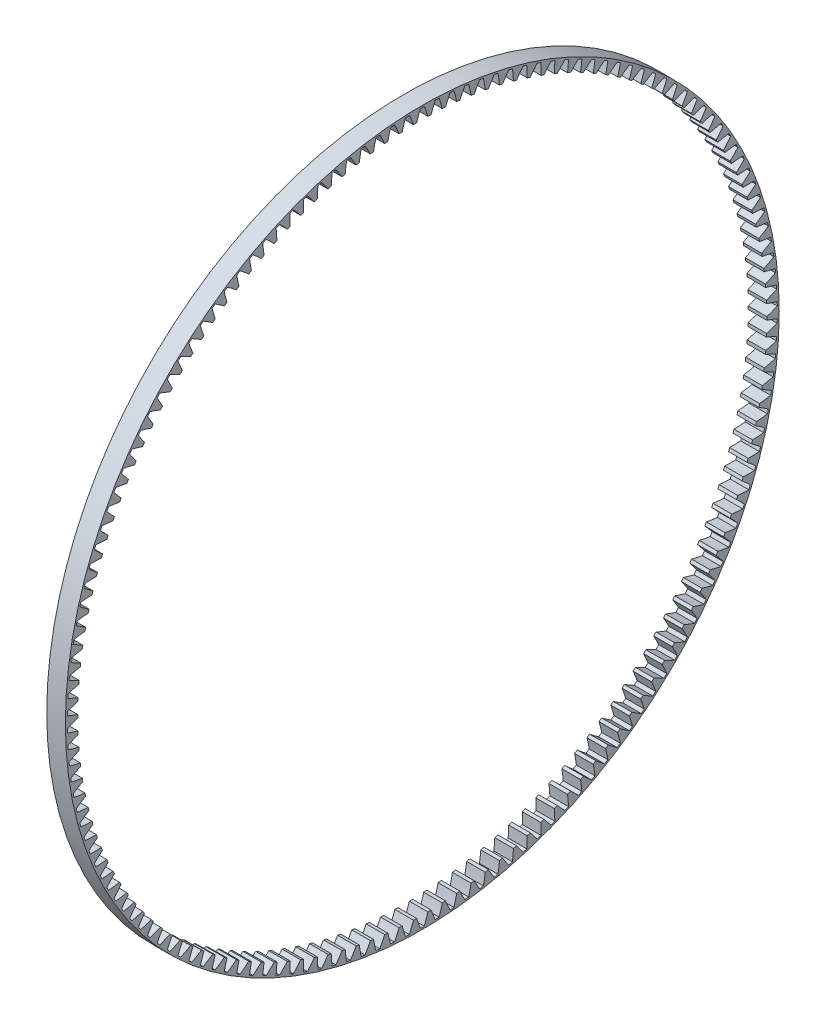
SolidWorks part; units mm, degrees
ref_plane "Plane1" through (0, 0, 0) normal (0, 0, 1) x (1, 0, 0)
ref_plane "Plane2" through (0, 0, 0) normal (0, 1, 0) x (1, 0, 0)
ref_plane "Plane3" through (0, 0, 0) normal (1, 0, 0) x (0, 0, -1)
sketch "HoldingSke" plane through (0, 0, 0) normal (0, 1, 0) x (1, 0, 0)
  line L0 (0, 0) -> (-0.2887, -0.1667)
  line L1 (-15, 0) -> (100, 0) construction
  line L2 (0, 0) -> (-2.1039, 2.3779)
  line L3 (0, 0) -> (-11.863, 4.5341)
  line L4 (0, 0) -> (-7.479, 4.318)
  line L5 (0, 0) -> (-23.7986, -8.8762)
  line L6 (0, 0) -> (-10.5278, -7.1032)
  line L7 (-2.1039, 2.3779) -> (3.3635, 27.1825)
  line L8 (-76.2, 5.3779) -> (-54.61, 5.3779)
  line L9 (-71.009, 38.7566) -> (-53.1078, 45.2721)
  line L10 (-76.2, 71.12) -> (104.1128, 71.12)
  line L11 (0, 0) -> (-12, 0)
  line L12 (-76.2, 101.6) -> (-76.093, 101.6)
  line L13 (24.9733, 27.94) -> (52.9518, 28.4284)
  line L14 (24.9733, 27.94) -> (24.9743, 27.94)
  line L15 (24.9733, 27.94) -> (100.4006, 29.5858)
  circle A0 centre (0, 0) radius 230
  circle A1 centre (0, 0) radius 12.7
  circle A2 centre (0, 0) radius 12.7
  dimension "Num_teeth" = 150
  dimension "Pitch_radius" = 180.3128
  dimension "Width" = 12
  dimension "Diameter" = 460
sketch "BasProSke" plane through (0, 0, 0) normal (0, 1, 0) x (1, 0, 0)
  line L0 (-10, 0) -> (60, 0) construction
  line L1 (0, 222) -> (0, 230)
  line L2 (0, 222) -> (12, 222)
  line L3 (12, 222) -> (12, 230)
  line L4 (12, 230) -> (0, 230)
  dimension "Thickness" = 12
  dimension "Diameter" = 460
revolve "Base-Revolve" add sketch "BasProSke" angle 360 about L0
sketch "TooCutSke" plane through (0, 0, 0) normal (1, 0, 0) x (0, 0, -1)
  line L3 (2.6237, 224.9847) -> (2.6237, 53.6633) construction
  line L4 (0, 0) -> (0, 59.563) construction
  line L5 (0, 0) -> (-1.4309, 68.3125) construction
  line L6 (-103.6779, 188.1578) -> (33.8494, 191.0385) construction
  circle A0 centre (0, 0) radius 225 construction
  circle A1 centre (0, 0) radius 228.751 construction
  circle A2 centre (0, 0) radius 190.2878 construction
  circle A3 centre (0, 0) radius 221.9746 construction
  arc A4 (3.6285, 221.9449) -> (1.2445, 228.7476) centre (-103.6779, 188.1578) ccw
  arc A5 (3.6285, 221.9449) -> (-3.6285, 221.9449) centre (0, 0) ccw
  arc A6 (1.2445, 228.7476) -> (-1.2445, 228.7476) centre (0, 0) ccw
  arc A7 (-1.2445, 228.7476) -> (-3.6285, 221.9449) centre (103.6779, 188.1578) ccw
extrude "ToothCut" cut sketch "TooCutSke" along normal through all
fillet "Breaks" [suppressed] radius 0.3
fillet "RootFillets" [suppressed] radius 0.751
pattern_circular "TeethCuts" count 150 every 2.4 about axis through (-10, 0, 0) along (1, 0, 0) of "RootFillets", "Breaks", "ToothCut"
equation "' \"Module@HoldingSke\" = 6.35"
equation "' \"Num_teeth@HoldingSke\" = 24"
equation "' \"Ap@HoldingSke\" =  14.5"
equation "' \"Ap@HoldingSke\" = 14.5"
equation "' \"Width@HoldingSke\" = 12"
equation "' \"Diameter@HoldingSke\" = 8 * 25.4"
equation "' \"Show_teeth@HoldingSke\" = 100"
equation "' \"Backlash@HoldingSke\" = 0.009 * 25.4"
equation "' \"Addendum_fac@HoldingSke\" = 1.0"
equation "' \"Dedendum_fac@HoldingSke\" = 1.25"
equation "' \"Dedendum_add@HoldingSke\" = 0.00005 * 25.4"
equation "' \"Clearance_fac@HoldingSke\" = 0.25"
equation "\"Pitch@HoldingSke\" = 1 / \"Module@HoldingSke\" "
equation "\"Overcut_dia@TooCutSke\" = (\"Num_teeth@HoldingSke\" - 2 * \"Addendum_fac@HoldingSke\") / \"Pitch@HoldingSke\" - 0.002 * 25.4"
equation "\"Pitch_dia@TooCutSke\" = \"Num_teeth@HoldingSke\" / \"Pitch@HoldingSke\""
equation "\"Base_dia@TooCutSke\" = \"Num_teeth@HoldingSke\" / \"Pitch@HoldingSke\" * cos((\"Ap@HoldingSke\"  * 3.14159265 / 180)) * 0.90"
equation "\"Root_dia@TooCutSke\" = \"Num_teeth@HoldingSke\"  / \"Pitch@HoldingSke\" + 2 *  \"Dedendum_fac@HoldingSke\"/ \"Pitch@HoldingSke\" + \"Dedendum_add@HoldingSke\" * 2"
equation "\"Half_ang@TooCutSke\" = 180 / \"Num_teeth@HoldingSke\""
equation "\"Half_CT@TooCutSke\" = \"Num_teeth@HoldingSke\" / \"Pitch@HoldingSke\" * sin((3.14159265 / 2 / \"Num_teeth@HoldingSke\")) / 2 + 10 * \"Backlash@HoldingSke\" / 4"
equation "\"Flank_rad@TooCutSke\" = \"Num_teeth@HoldingSke\" / \"Pitch@HoldingSke\" / 4"
equation "\"Radius@RootFillets\"= \"Clearance_fac@HoldingSke\" / \"Pitch@HoldingSke\" + \"Dedendum_add@HoldingSke\""
equation "\"Break_rad@Breaks\" = 0.02 / \"Pitch@HoldingSke\" * 5"
equation "\"Num_teeth@TeethCuts\" = int( \"Show_teeth@HoldingSke\" ) + 1"
equation "\"Num_teeth@TeethCuts\" = ((sgn( \"Num_teeth@TeethCuts\" - \"Num_teeth@HoldingSke\" )-1)*( \"Num_teeth@TeethCuts\" - \"Num_teeth@HoldingSke\" ))/-2+ \"Num_teeth@HoldingSke\""
equation "\"Num_teeth@TeethCuts\" = ((sgn( \"Num_teeth@TeethCuts\" - 2.0)+1)*( \"Num_teeth@TeethCuts\" - 2.0))/2 +2.0"
equation "\"Angle@TeethCuts\" = 360.0 / \"Num_teeth@HoldingSke\""
equation "\"Diameter@BasProSke\" = \"Num_teeth@HoldingSke\"  / \"Pitch@HoldingSke\" + 2 *  \"Dedendum_fac@HoldingSke\"/ \"Pitch@HoldingSke\" + \"Dedendum_add@HoldingSke\" * 2 + 0.002 * 25.4"
equation "\"Diameter@BasProSke\" = ((sgn( \"Diameter@BasProSke\"  - \"Diameter@HoldingSke\" )+1)*( \"Diameter@BasProSke\"  - \"Diameter@HoldingSke\" ))/2 + \"Diameter@HoldingSke\""
equation "\"Inside_diameter@BasProSke\" =  (\"Num_teeth@HoldingSke\" - 2 * \"Addendum_fac@HoldingSke\") / \"Pitch@HoldingSke\" "
equation "\"Thickness@BasProSke\"  = \"Width@HoldingSke\""
